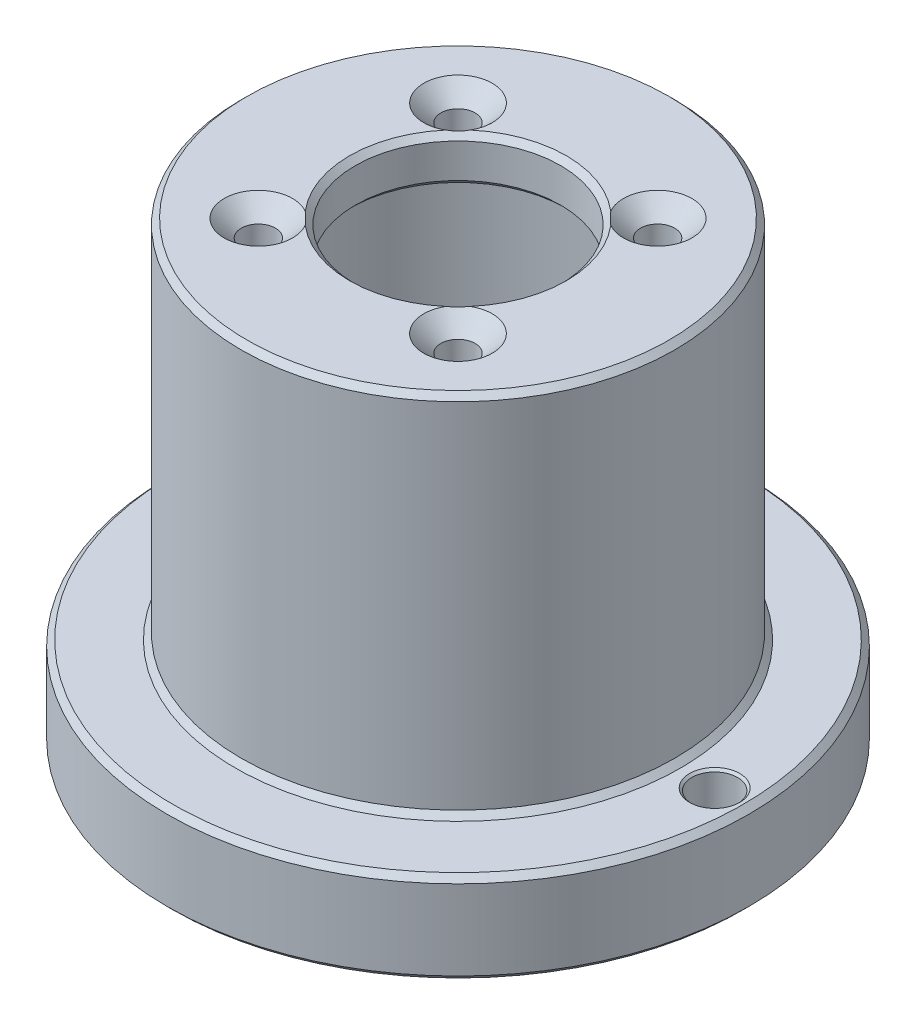
SolidWorks part; units mm, degrees
ref_plane "Front" through (0, 0, 0) normal (0, 0, 1) x (1, 0, 0)
ref_plane "Top" through (0, 0, 0) normal (0, 1, 0) x (1, 0, 0)
ref_plane "Right" through (0, 0, 0) normal (1, 0, 0) x (0, 0, -1)
sketch "Esquisse1" plane through (0, 0, 0) normal (0, 0, 1) x (1, 0, 0)
  line L0 (0, 0) -> (0, 40) construction
  line L1 (-15, 0) -> (-25.5, 0)
  line L2 (-25.5, 0) -> (-25.5, 8)
  line L3 (-25.5, 8) -> (-19, 8)
  line L4 (-19, 8) -> (-19, 40)
  line L5 (-19, 40) -> (-9, 40)
  line L6 (-9, 40) -> (-9, 36)
  line L7 (-9, 36) -> (-15, 36)
  line L8 (-15, 36) -> (-15, 0)
  point P5 (-4.2859, 37.4561)
  point P10 (-4.3412, 40.7291)
  point P13 (-9, 40.7291)
  point P14 (-9, 37.6999)
  dimension "D1" = 9
  dimension "D2" = 19
  dimension "D3" = 15
  dimension "D4" = 40
  dimension "D5" = 4
  dimension "D6" = 25.5
  dimension "D7" = 8
revolve "Révolution1" add sketch "Esquisse1" angle 360 about L0
sketch "Esquisse2" plane through (0, 40, 0) normal (0, 1, 0) x (1, 0, 0)
  line L1 (8.75, -8.75) -> (-8.75, -8.75) construction
  line L2 (8.75, -8.75) -> (8.75, 8.75) construction
  line L3 (8.75, 8.75) -> (-8.75, 8.75) construction
  line L4 (-8.75, -8.75) -> (-8.75, 8.75) construction
  line L5 (8.75, -8.75) -> (-8.75, 8.75) construction
  line L6 (8.75, 8.75) -> (-8.75, -8.75) construction
  circle A0 centre (-8.75, 8.75) radius 1.5
  circle A1 centre (8.75, 8.75) radius 1.5
  circle A2 centre (8.75, -8.75) radius 1.5
  circle A3 centre (-8.75, -8.75) radius 1.5
  point P0 (0, 0)
  dimension "D1" = 3
  dimension "D2" = 17.5
extrude "Enlèv. mat.-Extru.1" cut sketch "Esquisse2" against normal blind 10
chamfer "Chanfrein1" distance 1.5 angle 45 4 edges at (-8.75, 40, 10.25) (8.75, 40, 10.25) (8.75, 40, -7.25) (-8.75, 40, -7.25)
sketch "Esquisse3" plane through (0, 8, 0) normal (0, 1, 0) x (1, 0, 0)
  line L0 (22.5, 0) -> (-22.5, 0) construction
  circle A0 centre (-22.5, 0) radius 2
  circle A1 centre (22.5, 0) radius 2
  point P4 (0, 0)
  point P9 (0, 0)
  dimension "D1" = 4
  dimension "D2" = 45
extrude "Enlèv. mat.-Extru.2" cut sketch "Esquisse3" against normal blind 10
chamfer "Chanfrein2" distance 0.2 angle 45 8 edges at (22.5, 0, 2) (22.5, 8, 2) (-8.75, 36, 10.25) (8.75, 36, 10.25) (8.75, 36, -7.25) (-8.75, 36, -7.25) (-22.5, 8, 2) (-22.5, 0, 2)
chamfer "Chanfrein3" distance 0.5 angle 45 8 edges at (0, 0, -15) (0, 36, -15) (0, 0, -25.5) (0, 8, -25.5) (0, 8, -19) (0, 40, -19) (0, 40, -9) (0, 36, -9)
